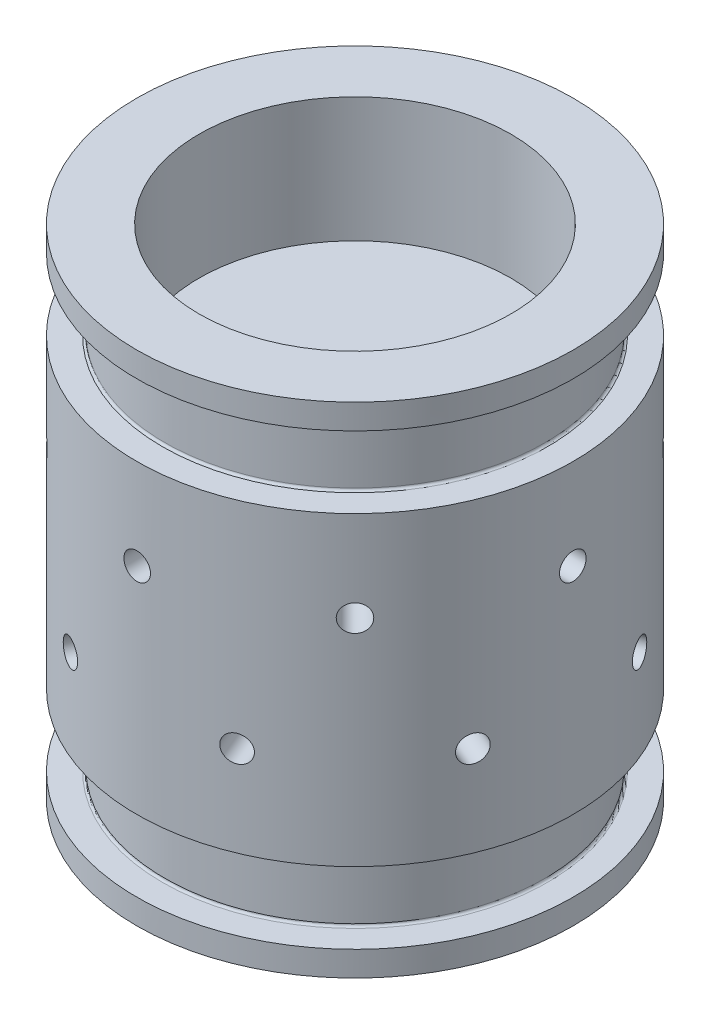
SolidWorks part; units mm, degrees
material "6063-T6"
ref_plane "Front Plane" through (0, 0, 0) normal (0, 0, 1) x (1, 0, 0)
ref_plane "Top Plane" through (0, 0, 0) normal (0, 1, 0) x (1, 0, 0)
ref_plane "Right Plane" through (0, 0, 0) normal (1, 0, 0) x (0, 0, -1)
sketch "Sketch1" plane through (0, 0, 0) normal (0, 1, 0) x (1, 0, 0)
  circle A0 centre (0, 0) radius 22.225
  dimension "D1" = 44.45
extrude "body" add sketch "Sketch1" along normal mid plane 50.8
sketch "Sketch2" plane through (0, 25.4, 0) normal (0, 1, 0) x (1, 0, 0)
  circle A0 centre (0, 0) radius 15.875
  dimension "D1" = 31.75
extrude "\"lightening hole\"" cut sketch "Sketch2" against normal blind 12.7
sketch "main-o-ring" plane through (0, 0, 0) normal (0, 0, 1) x (1, 0, 0)
  line L0 (0, 0) -> (0, 33.5592) construction
  line L1 (-22.225, 22.86) -> (-22.225, 15.5702)
  line L2 (-22.225, 22.86) -> (-19.6204, 22.86)
  line L3 (-19.3802, 22.6198) -> (-19.3802, 15.8104)
  line L4 (-19.6204, 15.5702) -> (-22.225, 15.5702)
  line L5 (22.225, 25.4) -> (-22.225, 25.4) construction
  arc A0 (-19.3802, 15.8104) -> (-19.6204, 15.5702) centre (-19.6204, 15.8104) cw
  arc A1 (-19.6204, 22.86) -> (-19.3802, 22.6198) centre (-19.6204, 22.6198) cw
  dimension "D5" = 0.2402
  dimension "D1" = 44.45
  dimension "D2" = 7.2898
  dimension "D3" = 2.54
  dimension "D4" = 2.8448
revolve "o-ring-main (with backup rings)" cut sketch "main-o-ring" angle 360 about L0
mirror "Top-Bottom Symmetry" about plane through (0, 0, 0) normal (0, 1, 0) of "o-ring-main (with backup rings)", "\"lightening hole\""
hole_wizard "#6-32 Tapped Hole1" positions "3DSketch1" profile "Sketch3" tap size "#6-32" standard "ANSI Inch"
sketch3d "3DSketch1"
  point P0 (-22.225, 6.35, 0)
  point P8 (0, 0, 0)
  dimension "D1" = 6.35
sketch "Sketch3" plane through (-22.225, 6.35, 0) normal (0, 1, 0) x (0, 0, 1)
  line L0 (0, 0) -> (0, 8.7629)
  line L1 (0, 8.7629) -> (1.3525, 7.9502)
  line L2 (1.3525, 7.9502) -> (1.3525, 0)
  line L5 (1.3525, 0) -> (0, 0)
  line L10 (0, 8.7629) -> (-1.3526, 7.9502) construction
  line L11 (0, -6.35) -> (0, 107.95) construction
  dimension "Tap Drill Dia." = 2.7051
  dimension "Tap Drill Depth" = 7.9502
  dimension "Drill Angle" = 118
cosmetic thread "Hole Thread1" parameters "D1"=7.0104, "D2"=3.5052
ref_plane "Offset Reference" through (-20.5332, 0, -8.5051) normal (-0.9239, 0, -0.3827) x (0, -1, 0)
hole_wizard "#6-32 Tapped Hole2" positions "3DSketch2" profile "Sketch4" tap size "#6-32" standard "ANSI Inch"
sketch3d "3DSketch2"
  point P0 (-20.5332, -6.35, -8.5051)
  point P3 (0, 0, 0)
  dimension "D1" = 6.35
sketch "Sketch4" plane through (-20.5332, -6.35, -8.5051) normal (0, 1, 0) x (-0.3827, 0, 0.9239)
  line L0 (0, 0) -> (0, 8.7629)
  line L1 (0, 8.7629) -> (1.3525, 7.9502)
  line L2 (1.3525, 7.9502) -> (1.3525, 0)
  line L5 (1.3525, 0) -> (0, 0)
  line L10 (0, 8.7629) -> (-1.3526, 7.9502) construction
  line L11 (0, -6.35) -> (0, 107.95) construction
  dimension "Tap Drill Dia." = 2.7051
  dimension "Tap Drill Depth" = 7.9502
  dimension "Drill Angle" = 118
cosmetic thread "Hole Thread9" parameters "D1"=7.0104, "D2"=3.5052
pattern_circular "Tapped Hole Pattern" count 8 over 360 about axis through (0, 25.4, 0) along (0, -1, 0) of "#6-32 Tapped Hole1", "#6-32 Tapped Hole2"
cosmetic thread "Hole Thread2" parameters "D1"=7.0104, "D2"=3.5052
cosmetic thread "Hole Thread3" parameters "D1"=7.0104, "D2"=3.5052
cosmetic thread "Hole Thread4" parameters "D1"=7.0104, "D2"=3.5052
cosmetic thread "Hole Thread5" parameters "D1"=7.0104, "D2"=3.5052
cosmetic thread "Hole Thread6" parameters "D1"=7.0104, "D2"=3.5052
cosmetic thread "Hole Thread7" parameters "D1"=7.0104, "D2"=3.5052
cosmetic thread "Hole Thread8" parameters "D1"=7.0104, "D2"=3.5052
cosmetic thread "Hole Thread10" parameters "D1"=7.0104, "D2"=3.5052
cosmetic thread "Hole Thread11" parameters "D1"=7.0104, "D2"=3.5052
cosmetic thread "Hole Thread12" parameters "D1"=7.0104, "D2"=3.5052
cosmetic thread "Hole Thread13" parameters "D1"=7.0104, "D2"=3.5052
cosmetic thread "Hole Thread14" parameters "D1"=7.0104, "D2"=3.5052
cosmetic thread "Hole Thread15" parameters "D1"=7.0104, "D2"=3.5052
cosmetic thread "Hole Thread16" parameters "D1"=7.0104, "D2"=3.5052
